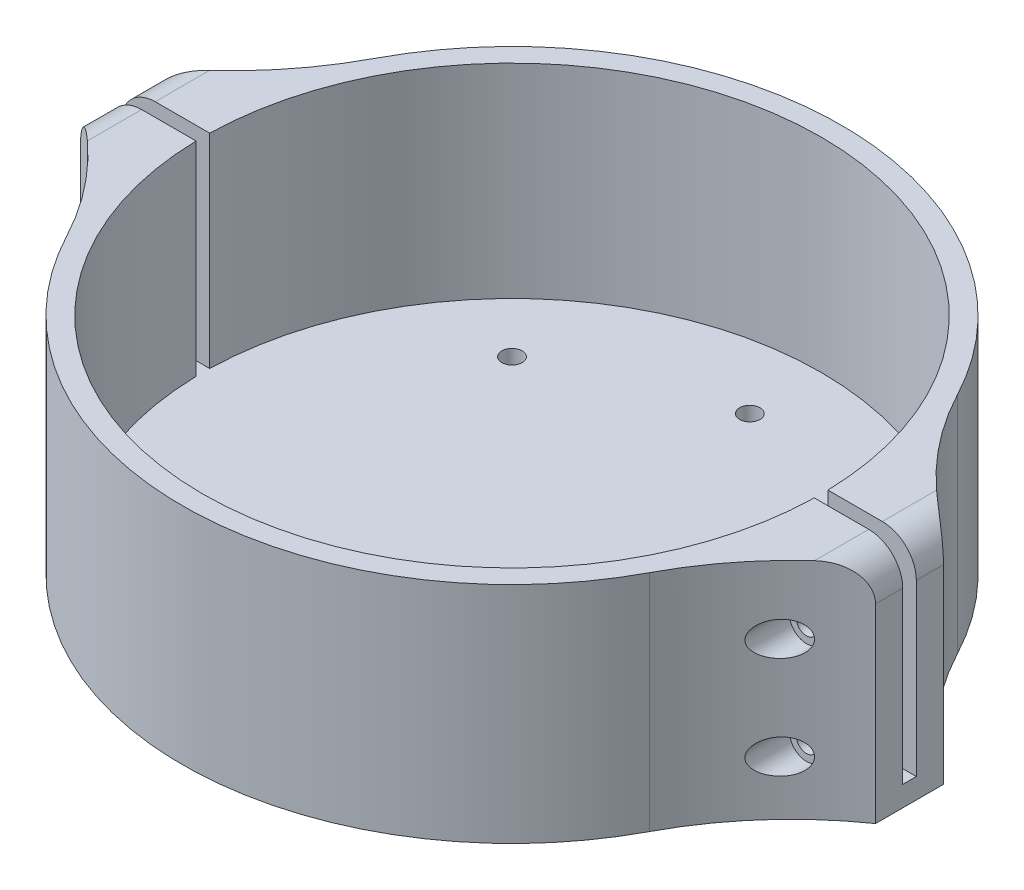
SolidWorks part; units mm, degrees
ref_plane "Front Plane" through (0, 0, 0) normal (0, 0, 1) x (1, 0, 0)
ref_plane "Top Plane" through (0, 0, 0) normal (0, 1, 0) x (1, 0, 0)
ref_plane "Right Plane" through (0, 0, 0) normal (1, 0, 0) x (0, 0, -1)
sketch "Sketch1" plane through (0, 0, 0) normal (0, 1, 0) x (1, 0, 0)
  circle A1 centre (0, 0) radius 45.5
  circle A2 centre (0, 0) radius 48.5
  dimension "D1" = 91
  dimension "D3" = 97
extrude "Boss-Extrude1" add sketch "Sketch1" along normal blind 30 contours A2 A1 region at (-47.1282, 0, 0)
sketch "Sketch2" plane through (0, 0, 0) normal (0, -1, 0) x (1, 0, 0)
  circle A0 centre (0, 0) radius 48.5
extrude "Boss-Extrude2" add sketch "Sketch2" along normal blind 3
sketch "Sketch3" plane through (0, -3, 0) normal (0, -1, 0) x (-1, 0, 0)
  circle A23 centre (0, -35) radius 1.5
  circle A24 centre (-24.7487, -24.7487) radius 1.5
  circle A25 centre (-35, 0) radius 1.5
  circle A26 centre (-24.7487, 24.7487) radius 1.5
  circle A27 centre (0, 35) radius 1.5
  circle A28 centre (24.7487, 24.7487) radius 1.5
  circle A29 centre (35, 0) radius 1.5
  circle A30 centre (24.7487, -24.7487) radius 1.5
  point P19 (0, 0)
  dimension "D1" = 3
  dimension "D2" = 35
extrude "Cut-Extrude2" cut sketch "Sketch3" against normal up to surface (3 mm away) up to face at (0, 0, 45.5)
sketch "Sketch6" plane through (0, 0, 0) normal (0, 0, 1) x (1, 0, 0)
  line L0 (-58.5, 30) -> (58.5, 30)
  line L1 (58.5, 30) -> (58.5, -3)
  line L2 (58.5, -3) -> (-58.5, -3)
  line L3 (-58.5, -3) -> (-58.5, 30)
  line L4 (-48.5, 30) -> (-48.5, -3) construction
  line L5 (48.5, -3) -> (48.5, 30) construction
  dimension "D1" = 10
  dimension "D2" = 10
  dimension "D3" = 33
extrude "Boss-Extrude4" add sketch "Sketch6" along normal mid plane 10
sketch "Sketch7" plane through (0, 30, 0) normal (0, 1, 0) x (1, 0, 0)
  line L0 (-58.5, -5) -> (-58.5, 5) construction
  line L1 (-58.5, 1) -> (-45.489, 1)
  line L2 (-58.5, 1) -> (-58.5, -1)
  line L3 (-58.5, -1) -> (-45.489, -1)
  line L4 (58.5, 1) -> (58.5, -1)
  line L5 (58.5, -5) -> (58.5, 5) construction
  line L6 (45.489, 1) -> (58.5, 1)
  line L7 (45.489, -1) -> (58.5, -1)
  arc A0 (-45.489, -1) -> (45.489, -1) centre (0, 0) ccw
  arc A1 (45.489, 1) -> (-45.489, 1) centre (0, 0) ccw
  point P11 (-58.5, 0)
  dimension "D1" = 2
extrude "Cut-Extrude3" cut sketch "Sketch7" along normal mid plane 60
fillet "Fillet1" radius 50 4 edges at (48.2416, 13.5, -5) (48.2416, 13.5, 5) (-48.2416, 13.5, -5) (-48.2416, 13.5, 5)
fillet "Fillet3" radius 5 4 edges at (58.5, 30, 3) (58.5, 30, -3) (-58.5, 30, 3) (-58.5, 30, -3)
sketch "Sketch8" plane through (0, 0, 0) normal (0, 0, 1) x (1, 0, 0)
  line L0 (-42.8809, 30) -> (-53.5, 30) construction
  line L1 (-58.5, 25) -> (-58.5, -3) construction
  circle A0 centre (-51, 20) radius 1.5
  circle A1 centre (-51, 5) radius 1.5
  dimension "D1" = 3
  dimension "D2" = 3
  dimension "D3" = 15
  dimension "D4" = 10
  dimension "D5" = 7.5
extrude "Cut-Extrude4" cut sketch "Sketch8" along normal mid plane 50
mirror "Mirror1" about plane through (0, 0, 0) normal (1, 0, 0) of "Cut-Extrude4"
ref_plane "Plane1" through (0, 0, 22.6601) normal (0, 0, 1) x (1, 0, 0)
sketch "Sketch9" plane through (0, 0, 22.6601) normal (0, 0, 1) x (1, 0, 0)
  circle A0 centre (-51, 20) radius 2.5
  circle A2 centre (-51, 5) radius 2.5
  dimension "D1" = 5
  dimension "D2" = 5
extrude "Cut-Extrude5" cut sketch "Sketch9" against normal blind 15
mirror "Mirror2" about plane through (0, 0, 0) normal (1, 0, 0) of "Cut-Extrude5"
ref_plane "Plane2" through (0, 0, -22.6601) normal (0, 0, -1) x (-1, 0, 0)
sketch "Sketch10" plane through (0, 0, -22.6601) normal (0, 0, -1) x (-1, 0, 0)
  circle A0 centre (-51, 20) radius 2.5
  circle A1 centre (-51, 5) radius 2.5
  dimension "D1" = 5
  dimension "D2" = 5
extrude "Cut-Extrude6" cut sketch "Sketch10" against normal blind 15
mirror "Mirror3" about plane through (0, 0, 0) normal (1, 0, 0) of "Cut-Extrude6"
